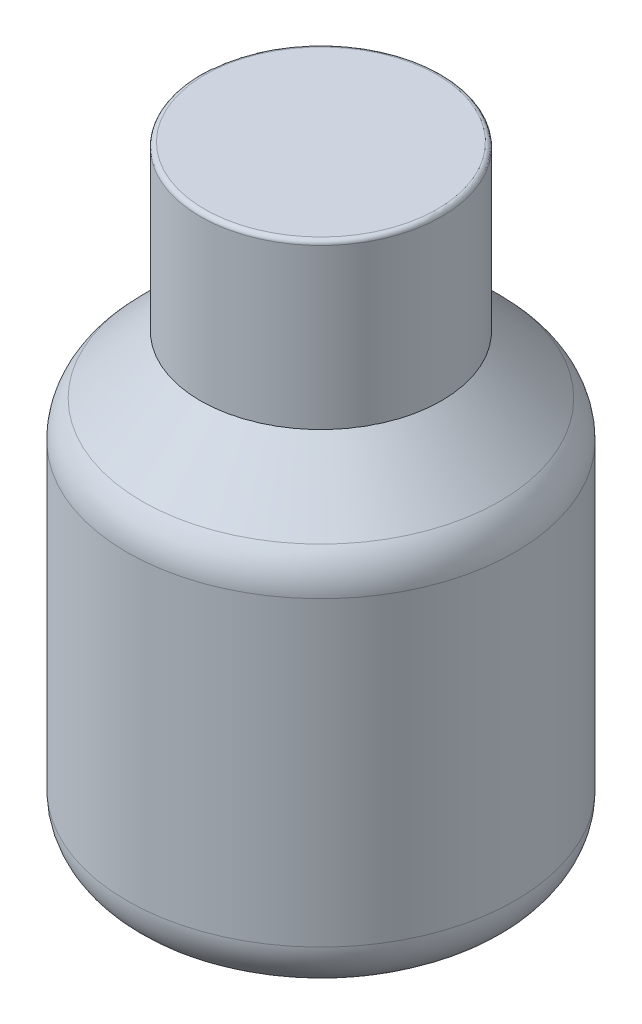
SolidWorks part; units mm, degrees
other "Tampa"
other "Frasco"
ref_plane "Plano frontal" through (0, 0, 0) normal (0, 0, 1) x (1, 0, 0)
ref_plane "Plano superior" through (0, 0, 0) normal (0, 1, 0) x (1, 0, 0)
ref_plane "Plano direito" through (0, 0, 0) normal (1, 0, 0) x (0, 0, -1)
sketch "Esboço1" plane through (0, 0, 0) normal (0, 0, 1) x (1, 0, 0)
  line L0 (0, 0) -> (0, 91.9776) construction
  line L1 (0, 0) -> (-16.5, 0)
  line L2 (-22.5, 6) -> (-22.5, 41.0147)
  line L3 (-20.7426, 45.2574) -> (-11, 55)
  line L4 (-11, 55) -> (-11, 68)
  line L5 (-11, 68) -> (-9.5, 68)
  line L6 (-9.5, 68) -> (-9.5, 70)
  line L7 (-9.5, 70) -> (0, 70)
  line L8 (0, 70) -> (0, 0)
  arc A0 (-22.5, 41.0147) -> (-20.7426, 45.2574) centre (-16.5, 41.0147) cw
  arc A1 (-16.5, 0) -> (-22.5, 6) centre (-16.5, 6) cw
  point P18 (-22.5, 43.5)
  point P21 (-22.5, 0)
  dimension "D9" = 6
  dimension "D1" = 45
  dimension "D2" = 70
  dimension "D3" = 43.5
  dimension "D4" = 22
  dimension "D5" = 45
  dimension "D6" = 2
  dimension "D7" = 1.5
  dimension "D8" = 13
revolve "Revolução1" add sketch "Esboço1" angle 360 about L8
sketch "Esboço2" plane through (0, 0, 0) normal (0, 0, 1) x (1, 0, 0)
  line L0 (14, 52) -> (14, 70.5)
  line L1 (20.7426, 45.2574) -> (11, 55) construction
  line L2 (13, 55) -> (13, 68)
  line L3 (13, 53) -> (13, 70)
  line L4 (14, 52) -> (13, 53)
  line L5 (14, 53) -> (14, 71) construction
  line L6 (9.5, 70) -> (-9.5, 70) construction
  line L7 (13, 70) -> (0, 70)
  line L8 (13, 53) -> (13, 71) construction
  line L9 (13.5, 71) -> (0, 71)
  line L10 (13, 71) -> (-9.5, 71) construction
  line L11 (0, 0) -> (0, 71) construction
  line L13 (13, 70) -> (-9.5, 70) construction
  line L14 (0, 71) -> (0, 70)
  arc A0 (14, 70.5) -> (13.5, 71) centre (13.5, 70.5) ccw
  dimension "D4" = 0.5
  dimension "D1" = 2
  dimension "D2" = 1
  dimension "D3" = 1
revolve "Revolução2" add sketch "Esboço2" angle 360 about L11
